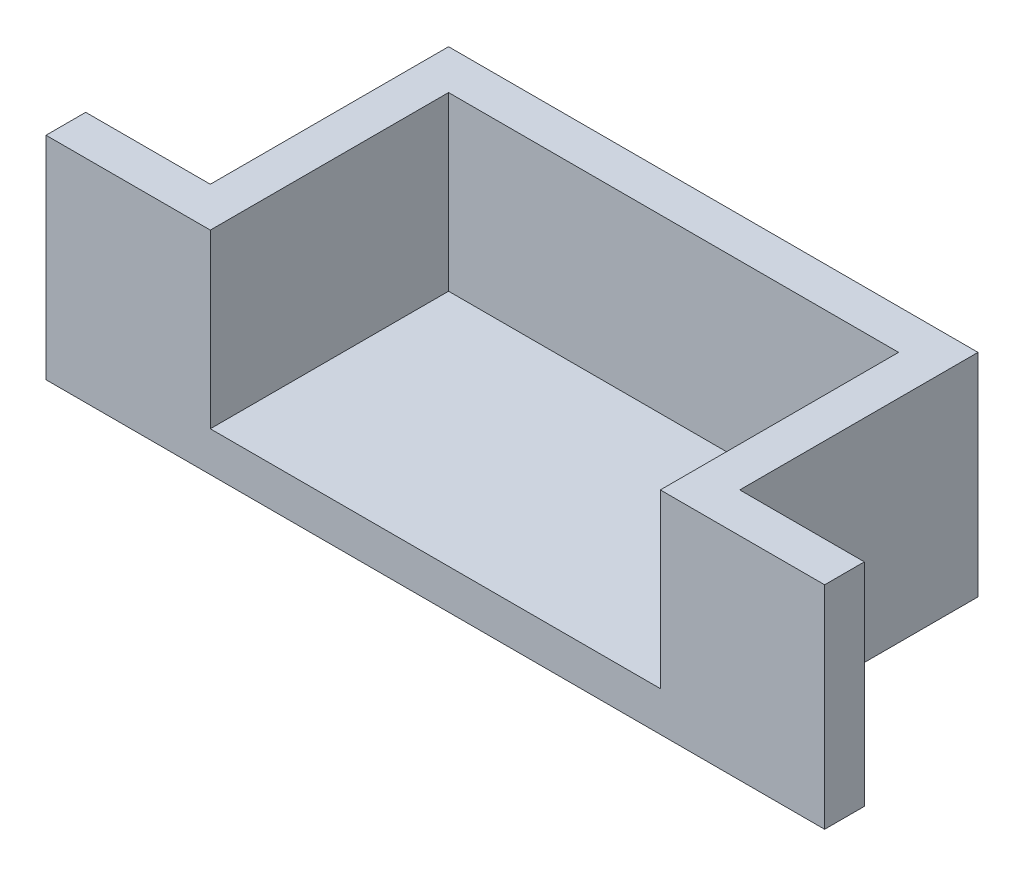
SolidWorks part; units mm, degrees
ref_plane "Front Plane" through (0, 0, 0) normal (0, 0, 1) x (1, 0, 0)
ref_plane "Top Plane" through (0, 0, 0) normal (0, 1, 0) x (1, 0, 0)
ref_plane "Right Plane" through (0, 0, 0) normal (1, 0, 0) x (0, 0, -1)
sketch "Sketch1" plane through (0, 0, 0) normal (0, 1, 0) x (1, 0, 0)
  line L0 (0, 0) -> (0, -15.5172) construction
  line L1 (-20, 7.9425) -> (20, 7.9425)
  line L2 (0, 7.9425) -> (0, 4.9425)
  line L3 (-20, 4.9425) -> (20, 4.9425)
  line L4 (20, 7.9425) -> (20, 4.9425)
  line L5 (20, 4.9425) -> (17, 4.9425)
  line L6 (20, 4.9425) -> (20, -10.0575)
  line L7 (20, -10.0575) -> (17, -10.0575)
  line L8 (17, 4.9425) -> (17, -10.0575)
  line L9 (17, -10.0575) -> (29.4138, -10.0575)
  line L10 (17, -10.0575) -> (17, -13.0575)
  line L11 (17, -13.0575) -> (29.4138, -13.0575)
  line L12 (29.4138, -10.0575) -> (29.4138, -13.0575)
  line L13 (-17, -13.0575) -> (-29.4138, -13.0575)
  line L14 (-29.4138, -10.0575) -> (-29.4138, -13.0575)
  line L15 (-17, -10.0575) -> (-29.4138, -10.0575)
  line L16 (-17, -10.0575) -> (-17, -13.0575)
  line L17 (-20, -10.0575) -> (-17, -10.0575)
  line L18 (-17, 4.9425) -> (-17, -10.0575)
  line L19 (-20, 4.9425) -> (-17, 4.9425)
  line L20 (-20, 4.9425) -> (-20, -10.0575)
  line L21 (-20, 7.9425) -> (-20, 4.9425)
  dimension "D1" = 20
  dimension "D2" = 3
  dimension "D3" = 3
  dimension "D4" = 3
  dimension "D5" = 18
extrude "Boss-Extrude1" add sketch "Sketch1" along normal blind 16 contours L3 L20 L15 L18 | L16 L15 L14 L13 | L1 L21 L3 L2 | L4 L1 L2 L3 | L3 L8 L7 L6 | L12 L9 L7 L10 L11 region at (-10, 0, -6.4425) region at (10, 0, -6.4425) region at (-18.5, 0, 2.5575) region at (-23.2069, 0, 11.5575) region at (18.5, 0, 2.5575) region at (23.2069, 0, 11.5575)
sketch "Sketch2" plane through (0, 0, 0) normal (0, 1, 0) x (1, 0, 0)
  line L1 (-17, 4.9425) -> (17, 4.9425)
  line L2 (-17, 4.9425) -> (-17, -13.0575)
  line L3 (-17, -13.0575) -> (17, -13.0575)
  line L4 (17, 4.9425) -> (17, -13.0575)
extrude "Boss-Extrude2" add sketch "Sketch2" along normal blind 3
